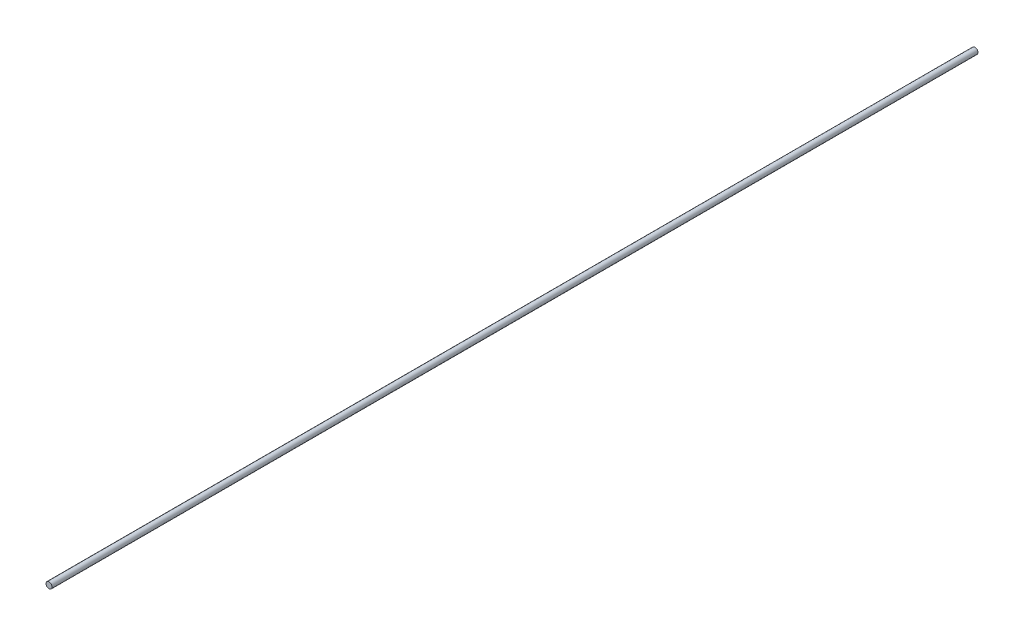
SolidWorks part; units mm, degrees
material "Hexcel AS4C (3000 Filaments)"
ref_plane "Front Plane" through (0, 0, 0) normal (0, 0, 1) x (1, 0, 0)
ref_plane "Top Plane" through (0, 0, 0) normal (0, 1, 0) x (1, 0, 0)
ref_plane "Right Plane" through (0, 0, 0) normal (1, 0, 0) x (0, 0, -1)
sketch "Sketch1" plane through (0, 0, 0) normal (0, 0, 1) x (1, 0, 0)
  circle A1 centre (-70.4276, -2.9481) radius 2.5
extrude "Boss-Extrude1" add sketch "Sketch1" against normal up to surface (761.9997 mm away)
